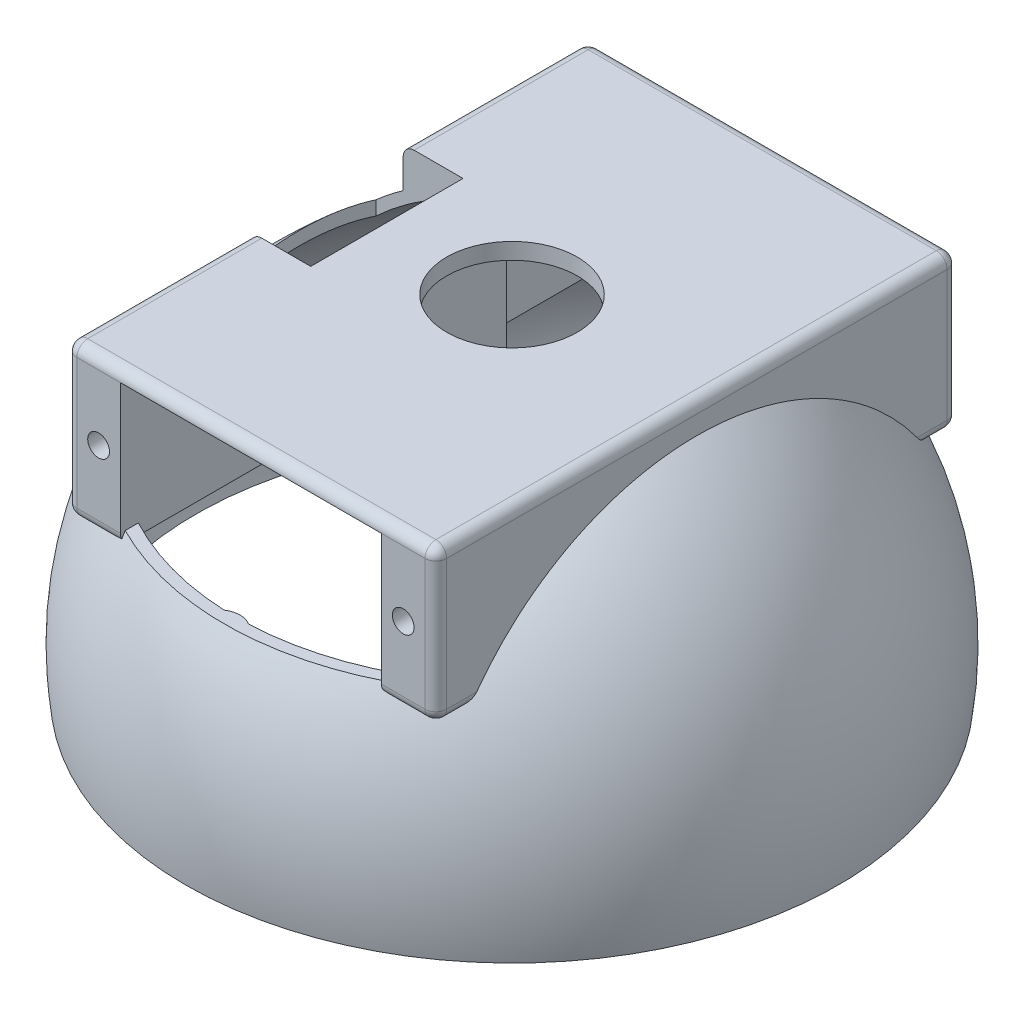
SolidWorks part; units mm, degrees
ref_plane "Front Plane" through (0, 0, 0) normal (0, 0, 1) x (1, 0, 0)
ref_plane "Top Plane" through (0, 0, 0) normal (0, 1, 0) x (1, 0, 0)
ref_plane "Right Plane" through (0, 0, 0) normal (1, 0, 0) x (0, 0, -1)
sketch "Sketch1" plane through (0, 0, 0) normal (0, 0, 1) x (1, 0, 0)
  line L0 (0, 0) -> (0, 34.5)
  line L1 (0, 0) -> (2, 0)
  line L2 (2, 0) -> (2, 33.5)
  line L3 (30, 0) -> (29.0588, 0)
  arc A0 (0, 34.5) -> (30, 0) centre (0, 4.2065) cw
  arc A1 (2, 33.5) -> (29.0588, 0) centre (0, 4.2065) cw
  dimension "D1" = 30
  dimension "D2" = 34.5
  dimension "D3" = 33.5
  dimension "D4" = 2
revolve "Revolve1" add sketch "Sketch1" angle 360 about L0
sketch "Sketch9" plane through (0, 0, 0) normal (0, 0, 1) x (1, 0, 0)
  line L0 (-12, 31) -> (-12, 18)
  line L1 (-17, 32) -> (17, 32)
  line L2 (-17, 32) -> (-17, 18)
  line L3 (-12, 18) -> (-17, 18)
  line L4 (17, 32) -> (17, 18)
  line L5 (-17, 32) -> (17, 18) construction
  line L6 (-17, 18) -> (17, 32) construction
  line L7 (-12, 31) -> (12, 31)
  line L8 (12, 31) -> (12, 18)
  line L9 (12, 18) -> (17, 18)
  point P0 (0, 25)
  point P5 (0, 25)
  dimension "D1" = 5
  dimension "D2" = 14
  dimension "D3" = 34
  dimension "D4" = 0
  dimension "D5" = 24
  dimension "D6" = 25
  dimension "D7" = 13
extrude "Boss-Extrude2" add sketch "Sketch9" along normal blind 15 from offset 9
sketch "Sketch10" plane through (0, 0, 0) normal (0, 0, 1) x (1, 0, 0)
  line L0 (12, 31) -> (12, 18)
  line L1 (17, 32) -> (-17, 32)
  line L2 (17, 32) -> (17, 18)
  line L3 (12, 18) -> (17, 18)
  line L4 (-17, 32) -> (-17, 18)
  line L5 (17, 32) -> (-17, 18) construction
  line L6 (17, 18) -> (-17, 32) construction
  line L7 (12, 31) -> (-12, 31)
  line L8 (-17, 18) -> (-12, 18)
  line L9 (-12, 18) -> (-12, 31)
  point P0 (0, 25)
  point P5 (0, 25)
  dimension "D1" = 34
  dimension "D2" = 14
  dimension "D3" = 5
  dimension "D4" = 0
  dimension "D5" = 24
  dimension "D6" = 13
  dimension "D7" = 25
extrude "Boss-Extrude4" add sketch "Sketch10" against normal blind 15 from offset 9 offset against normal yes
sketch "Sketch2" plane through (0, 0, 0) normal (0, -1, 0) x (1, 0, 0)
  circle A0 centre (0, 0) radius 13.165
  dimension "D1" = 26.33
extrude "Cut-Extrude1" cut sketch "Sketch2" against normal blind 35
sketch "Sketch3" plane through (0, 0, 0) normal (0, -1, 0) x (1, 0, 0)
  circle A0 centre (0, -27) radius 2
  circle A1 centre (0, 27) radius 2
  dimension "D1" = 4
  dimension "D3" = 4
  dimension "D4" = 27
  dimension "D2" = 27
extrude "Boss-Extrude1" add sketch "Sketch3" against normal up to next
sketch "Sketch4" plane through (0, 0, 0) normal (0, -1, 0) x (1, 0, 0)
  circle A0 centre (0, -27) radius 1.15
  circle A1 centre (0, 27) radius 1.15
  dimension "D1" = 2.3
  dimension "D2" = 2.3
extrude "Cut-Extrude2" cut sketch "Sketch4" against normal blind 6
sketch "Sketch7" plane through (0, 0, 0) normal (0, 0, 1) x (1, 0, 0)
  line L1 (12, 31) -> (-12, 31)
  line L2 (12, 31) -> (12, 19)
  line L3 (12, 19) -> (-12, 19)
  line L4 (-12, 31) -> (-12, 19)
  line L5 (12, 31) -> (-12, 19) construction
  line L6 (12, 19) -> (-12, 31) construction
  line L7 (-29.0588, 0) -> (29.0588, 0) construction
  point P0 (0, 25)
  dimension "D1" = 24
  dimension "D2" = 0
  dimension "D3" = 12
  dimension "D4" = 19
extrude "Cut-Extrude3" cut sketch "Sketch7" against normal blind 33 from offset 5 offset against normal yes
sketch "Sketch8" plane through (0, 0, 0) normal (0, 0, 1) x (1, 0, 0)
  line L1 (-12, 31) -> (12, 31)
  line L2 (-12, 31) -> (-12, 19)
  line L3 (-12, 19) -> (12, 19)
  line L4 (12, 31) -> (12, 19)
  line L5 (-12, 31) -> (12, 19) construction
  line L6 (-12, 19) -> (12, 31) construction
  line L7 (-29.0588, 0) -> (29.0588, 0) construction
  point P0 (0, 25)
  dimension "D1" = 19
  dimension "D2" = 12
  dimension "D3" = 24
  dimension "D4" = 0
extrude "Cut-Extrude4" cut sketch "Sketch8" along normal blind 33 from offset 5
sketch "Sketch13" plane through (0, 0, -9) normal (0, 0, 1) x (1, 0, 0)
  line L0 (-9.5991, 32) -> (-17, 32)
  line L1 (-17, 32) -> (-17, 27.6094)
  arc A0 (-12, 30.5256) -> (-17, 27.6094) centre (0, 4.2065) ccw construction
  spline S0 degree 2 poles (-17, 27.6094) (-13.4032, 29.9784) (-9.5991, 32) knots 0 0 0 1 1 1
extrude "Boss-Extrude5" add sketch "Sketch13" along normal blind 18
sketch "Sketch14" plane through (0, 0, -9) normal (0, 0, 1) x (1, 0, 0)
  line L0 (17, 27.6094) -> (17, 32)
  line L1 (17, 32) -> (9.5991, 32)
  arc A0 (17, 27.6094) -> (12, 30.5256) centre (0, 4.2065) ccw construction
  spline S0 degree 2 poles (17, 27.6094) (13.363, 29.9119) (9.5991, 32) knots 0 0 0 1 1 1
extrude "Boss-Extrude6" add sketch "Sketch14" along normal blind 18 separate body
fillet "Fillet4" radius 1 10 edges at (17, 32, -16.5) (17, 25, -24) (0, 32, -24) (-17, 25, -24) (-17, 32, -16.5) (-17, 32, 16.5) (-17, 25, 24) (0, 32, 24) (17, 32, 16.5) (17, 25, 24)
fillet "Fillet5" radius 1 1 edges at (-17, 32, 0)
fillet "Fillet6" radius 1 1 edges at (17, 32, 0)
sketch "Sketch18" plane through (0, 32, 0) normal (0, 1, 0) x (1, 0, 0)
  circle A0 centre (0, 0) radius 15.5
  circle A1 centre (0, 0) radius 6
  dimension "D1" = 31
  dimension "D2" = 12
extrude "Boss-Extrude7" add sketch "Sketch18" against normal blind 1.5
fillet "Fillet7" radius 1 16 edges at (-12.1537, 18.1343, 24) (12.1537, 18.1343, 24) (17, 18, -21.9694) (-14.1529, 18, -24) (16.7071, 18, -23.7071) (-17, 18, -21.9694) (-16.7071, 18, -23.7071) (-17, 18, 21.9694) (-14.1529, 18, 24) (-16.7071, 18, 23.7071) (17, 18, 21.9694) (16.7071, 18, 23.7071) (14.1529, 18, 24) (12.1537, 18.1343, -24) (-12.1537, 18.1343, -24) (14.1529, 18, -24)
sketch "Sketch19" plane through (0, 0, 24) normal (0, 0, 1) x (1, 0, 0)
  line L1 (-16, 32) -> (16, 32) construction
  line L2 (17, 31) -> (17, 19) construction
  line L3 (-17, 19) -> (-17, 31) construction
  circle A0 centre (14, 25) radius 1
  circle A1 centre (-14, 25) radius 1
  dimension "D1" = 7
  dimension "D2" = 3
  dimension "D3" = 2
  dimension "D4" = 2
  dimension "D6" = 3
  dimension "D5" = 7
extrude "Cut-Extrude5" cut sketch "Sketch19" against normal blind 10
sketch "Sketch20" plane through (0, 0, -24) normal (0, 0, -1) x (-1, 0, 0)
  line L0 (-16, 32) -> (16, 32) construction
  line L1 (-17, 19) -> (-17, 31) construction
  line L2 (17, 31) -> (17, 19) construction
  circle A0 centre (-14, 25) radius 1
  circle A1 centre (14, 25) radius 1
  dimension "D1" = 2
  dimension "D4" = 2
  dimension "D2" = 7
  dimension "D3" = 3
  dimension "D5" = 7
  dimension "D6" = 3
extrude "Cut-Extrude6" cut sketch "Sketch20" against normal blind 10
sketch "Sketch21" plane through (0, 18, 0) normal (0, -1, 0) x (1, 0, 0)
  line L9 (12, 9) -> (14, 9)
  line L10 (12, 9) -> (12, 17)
  line L11 (12, 17) -> (14, 17)
  line L12 (14, 9) -> (14, 17)
  line L13 (12, -9) -> (14, -9)
  line L14 (12, -9) -> (12, -17)
  line L15 (12, -17) -> (14, -17)
  line L16 (14, -9) -> (14, -17)
  dimension "D5" = 2
  dimension "D6" = 8
  dimension "D7" = 2
  dimension "D8" = 8
extrude "Cut-Extrude7" cut sketch "Sketch21" against normal blind 10
sketch3d "3DSketch1" plane through (0, 0, 0) normal (0, 0, 1) x (1, 0, 0)
  dimension "D1" = 9
sketch "Sketch24" plane through (0, 21.5, 0) normal (0, -1, 0) x (-1, 0, 0)
  line L1 (-17.5, -6) -> (-22.5, -6)
  line L2 (-17.5, -6) -> (-17.5, 6)
  line L3 (-17.5, 6) -> (-22.5, 6)
  line L4 (-22.5, -6) -> (-22.5, 6)
  line L5 (-17.5, -6) -> (-22.5, 6) construction
  line L6 (-17.5, 6) -> (-22.5, -6) construction
  line L7 (11.5, -6) -> (6.5, -6)
  line L8 (11.5, -6) -> (11.5, 6)
  line L9 (11.5, 6) -> (6.5, 6)
  line L10 (6.5, -6) -> (6.5, 6)
  line L11 (11.5, -6) -> (6.5, 6) construction
  line L12 (11.5, 6) -> (6.5, -6) construction
  circle A0 centre (-20, 0) radius 1.1
  circle A1 centre (9, 0) radius 1.1
  dimension "D1" = 2.2
  dimension "D2" = 2.2
  dimension "D4" = 9
  dimension "D3" = 20
  dimension "D5" = 5
  dimension "D6" = 5
  dimension "D7" = 12
  dimension "D8" = 12
extrude "Boss-Extrude10" add sketch "Sketch24" against normal up to next
sketch "Sketch25" plane through (0, 30.5, 0) normal (0, -1, 0) x (1, 0, 0)
  line L0 (-11.5, 6) -> (-11.5, -6) construction
  line L1 (-11.5, 7) -> (-19.5, 7)
  line L2 (-11.5, 7) -> (-11.5, -7)
  line L3 (-11.5, -7) -> (-19.5, -7)
  line L4 (-19.5, 7) -> (-19.5, -7)
  line L5 (-11.5, 7) -> (-19.5, -7) construction
  line L6 (-11.5, -7) -> (-19.5, 7) construction
  circle A0 centre (0, 0) radius 6 construction
  point P0 (-15.5, 0)
  dimension "D1" = 0
  dimension "D2" = 14
  dimension "D3" = 8
  dimension "D4" = 0
extrude "Cut-Extrude8" cut sketch "Sketch25" along normal up to next and the other way through all
